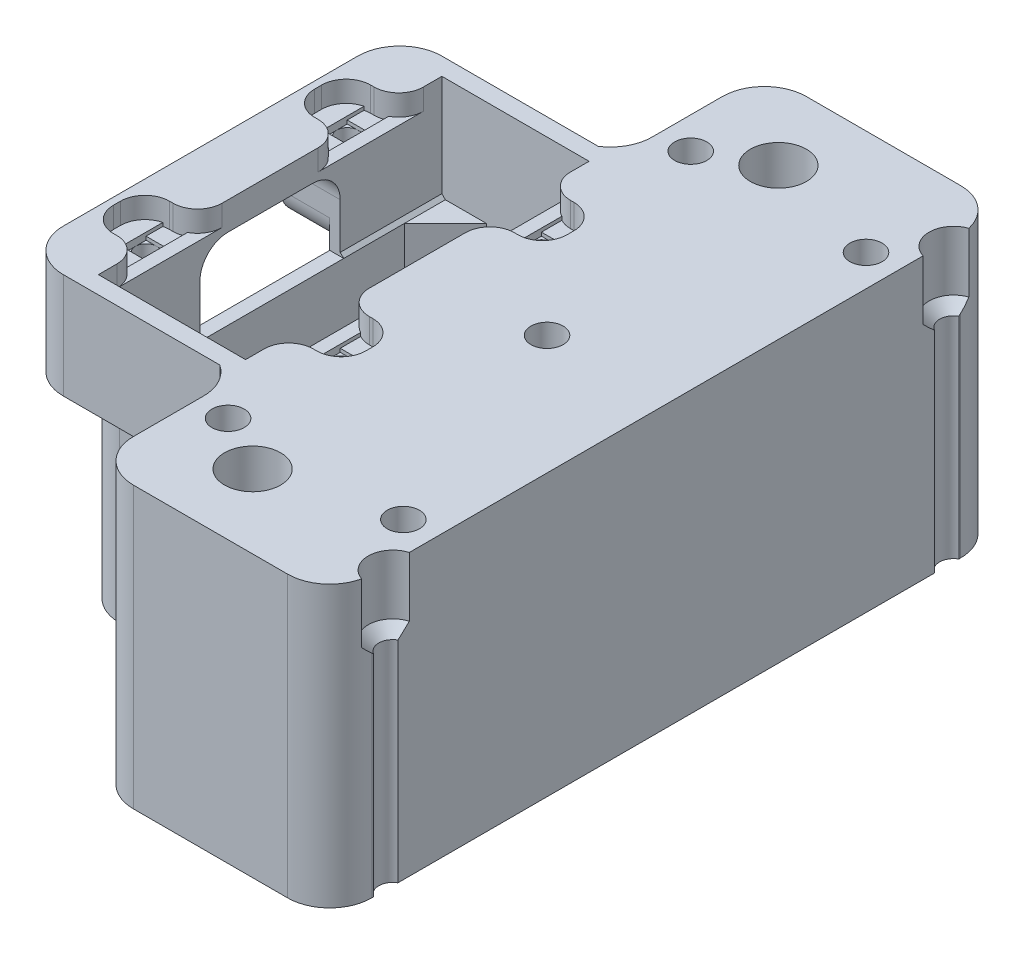
SolidWorks part; units mm, degrees
ref_plane "Płaszczyzna przednia" through (0, 0, 0) normal (0, 0, 1) x (1, 0, 0)
ref_plane "Płaszczyzna górna" through (0, 0, 0) normal (0, 1, 0) x (1, 0, 0)
ref_plane "Płaszczyzna prawa" through (0, 0, 0) normal (1, 0, 0) x (0, 0, -1)
sketch "Szkic1" plane through (0, 0, 0) normal (0, 1, 0) x (1, 0, 0)
  line L0 (0, 14.5) -> (0, -14.5) construction
  line L1 (10, 14.5) -> (10, -14.5)
  line L2 (-10, 14.5) -> (-10, -14.5)
  line L4 (-12, 26) -> (12, 26)
  line L5 (-12, 26) -> (-12, -26)
  line L6 (-12, -26) -> (12, -26)
  line L7 (12, 26) -> (12, -26)
  line L8 (-12, 26) -> (12, -26) construction
  line L9 (-12, -26) -> (12, 26) construction
  arc A0 (10, 14.5) -> (-10, 14.5) centre (0, 14.5) ccw
  arc A1 (-10, -14.5) -> (10, -14.5) centre (0, -14.5) ccw
  point P2 (0, 0)
  point P8 (0, 0)
  dimension "D2" = 10
  dimension "D1" = 29
  dimension "D3" = 24
  dimension "D4" = 52
extrude "Dodanie-wyciągnięcie1" add sketch "Szkic1" along normal blind 25
sketch "Szkic2" plane through (0, 25, 0) normal (0, 1, 0) x (1, 0, 0)
  line L1 (-10.5, 24.5) -> (10.5, 24.5)
  line L2 (-10.5, 24.5) -> (-10.5, -24.5)
  line L3 (-10.5, -24.5) -> (10.5, -24.5)
  line L4 (10.5, 24.5) -> (10.5, -24.5)
  line L5 (-10.5, 24.5) -> (10.5, -24.5) construction
  line L6 (-10.5, -24.5) -> (10.5, 24.5) construction
  line L7 (-13, 27) -> (13, 27)
  line L8 (-13, 27) -> (-13, -27)
  line L9 (-13, -27) -> (13, -27)
  line L10 (13, 27) -> (13, -27)
  line L11 (-13, 27) -> (13, -27) construction
  line L12 (-13, -27) -> (13, 27) construction
  point P0 (0, 0)
  point P7 (0, 0)
  dimension "D1" = 26
  dimension "D2" = 54
  dimension "D3" = 21
  dimension "D4" = 49
extrude "Dodanie-wyciągnięcie2" add sketch "Szkic2" along normal blind 12
sketch "Szkic3" plane through (0, 37, 0) normal (0, 1, 0) x (1, 0, 0)
  line L0 (13, -27) -> (13, 27) construction
  line L1 (-19, 27) -> (19, 27)
  line L2 (-19, 27) -> (-19, -27)
  line L3 (-19, -27) -> (19, -27)
  line L4 (19, 27) -> (19, -27)
  line L5 (-19, 27) -> (19, -27) construction
  line L6 (-19, -27) -> (19, 27) construction
  line L7 (-13, -27) -> (13, -27) construction
  line L9 (-10.5, 24.5) -> (10.5, 24.5)
  line L10 (-10.5, 24.5) -> (-10.5, -24.5)
  line L11 (-10.5, -24.5) -> (10.5, -24.5)
  line L12 (10.5, 24.5) -> (10.5, -24.5)
  line L13 (-10.5, 24.5) -> (10.5, -24.5) construction
  line L14 (-10.5, -24.5) -> (10.5, 24.5) construction
  point P0 (0, 0)
  point P10 (0, 0)
  dimension "D1" = 6
extrude "Dodanie-wyciągnięcie3" add sketch "Szkic3" against normal blind 12
sketch "Szkic4" plane through (0, 37, 0) normal (0, 1, 0) x (1, 0, 0)
  line L0 (10, 24.5) -> (-10, 24.5)
  line L1 (-19, 27) -> (19, 27)
  line L2 (-19, 27) -> (-19, -27)
  line L3 (-19, -27) -> (19, -27)
  line L4 (19, 27) -> (19, -27)
  line L5 (-19, 27) -> (19, -27) construction
  line L6 (-19, -27) -> (19, 27) construction
  line L7 (10.5, 24.5) -> (-10.5, 24.5) construction
  line L8 (-10, 24.5) -> (-10, 18.35)
  line L9 (-10, 18.35) -> (-18, 18.35)
  line L10 (-18, 18.35) -> (-18, 10.35)
  line L11 (-18, 10.35) -> (-10, 10.35)
  line L12 (-10, 10.35) -> (-10, -10.35)
  line L13 (-10, -10.35) -> (-18, -10.35)
  line L14 (-18, -10.35) -> (-18, -18.35)
  line L15 (-18, -18.35) -> (-10, -18.35)
  line L16 (10, -24.5) -> (-10, -24.5)
  line L17 (-10.5, -24.5) -> (10.5, -24.5) construction
  line L18 (-10, -24.5) -> (-10, -18.35)
  line L19 (0, -20.35) -> (0, 20.35) construction
  line L20 (10, -24.5) -> (10, -18.35)
  line L21 (18, -18.35) -> (10, -18.35)
  line L22 (18, -10.35) -> (18, -18.35)
  line L23 (10, -10.35) -> (18, -10.35)
  line L24 (10, 10.35) -> (10, -10.35)
  line L25 (18, 10.35) -> (10, 10.35)
  line L26 (18, 18.35) -> (18, 10.35)
  line L27 (10, 18.35) -> (18, 18.35)
  line L28 (10, 24.5) -> (10, 18.35)
  line L29 (19, 27) -> (19, -27)
  point P0 (0, 0)
  point P24 (-18, -14.35)
  point P25 (-18, 14.35)
  point P29 (0, -24.5)
  point P37 (0, 24.5)
  line M8 (-19, -27) -> (19, -27)
  line M9 (19, -27) -> (19, 27)
  line M10 (19, 27) -> (-19, 27)
  line M11 (-19, 27) -> (-19, -27)
  line M12 (-10.5, 24.5) -> (10.5, 24.5)
  line M13 (10.5, 24.5) -> (10.5, -24.5)
  line M14 (10.5, -24.5) -> (-10.5, -24.5)
  line M15 (-10.5, -24.5) -> (-10.5, 24.5)
  dimension "D1" = 8
  dimension "D2" = 8
  dimension "D3" = 28.7
  dimension "D4" = 8
  dimension "D5" = 1
extrude "Dodanie-wyciągnięcie4" add sketch "Szkic4" along normal blind 3 contours L27 L26 L25 L23 L22 L21 L15 L14 L13 L11 L10 L9 M11 M8 M9 M10 M13 M14 M15 M12 region at (0, 37, -26.3397)
fillet "Zaokrąglenie1" radius 3.5 16 edges at (-18, 38.5, -10.35) (-18, 38.5, -18.35) (-18, 38.5, 10.35) (-18, 38.5, 18.35) (18, 38.5, -10.35) (18, 38.5, -18.35) (18, 38.5, 10.35) (18, 38.5, 18.35) (10.5, 38.5, 10.35) (10.5, 38.5, 18.35) (10.5, 38.5, -18.35) (10.5, 38.5, -10.35) (-10.5, 38.5, -18.35) (-10.5, 38.5, -10.35) (-10.5, 38.5, 10.35) (-10.5, 38.5, 18.35)
sketch "Szkic5" plane through (0, 37, 0) normal (0, 1, 0) x (1, 0, 0)
  line L0 (18, -14.35) -> (13.85, -14.35) construction
  line L3 (18, -13.85) -> (18, -14.85) construction
  line L6 (18, 14.35) -> (13.85, 14.35) construction
  line L9 (18, 14.85) -> (18, 13.85) construction
  line L13 (0, -22) -> (0, 22) construction
  circle A0 centre (13.85, -14.35) radius 1.5
  circle A1 centre (13.85, 14.35) radius 1.5
  circle A2 centre (-13.85, -14.35) radius 1.5
  circle A3 centre (-13.85, 14.35) radius 1.5
  dimension "D1" = 3
  dimension "D2" = 3
  dimension "D3" = 4.15
  dimension "D4" = 4.15
extrude "Wytnij-wyciągnięcie1" cut sketch "Szkic5" against normal blind 8
sketch "Szkic7" plane through (-19, 0, 0) normal (-1, 0, 0) x (0, 0, 1)
  line L1 (-10, 36) -> (10, 36)
  line L2 (-10, 36) -> (-10, 25)
  line L3 (-10, 25) -> (10, 25)
  line L4 (10, 36) -> (10, 25)
  line L5 (-10, 36) -> (10, 25) construction
  line L6 (-10, 25) -> (10, 36) construction
  line L7 (0, 30.5) -> (0, 40) construction
  line L10 (-27, 40) -> (27, 40) construction
  line L12 (-27, 25) -> (27, 25) construction
  point P0 (0, 30.5)
  dimension "D1" = 20
  dimension "D2" = 11
extrude "Wytnij-wyciągnięcie2" cut sketch "Szkic7" against normal up to next
sketch "Szkic8" plane through (0, 0, 0) normal (0, 1, 0) x (1, 0, 0)
  line L1 (12, -48) -> (46, -48)
  line L2 (12, -48) -> (12, 48)
  line L3 (12, 48) -> (46, 48)
  line L4 (46, -48) -> (46, 48)
  line L5 (12, -48) -> (46, 48) construction
  line L6 (12, 48) -> (46, -48) construction
  line L8 (14, 46) -> (44, 46)
  line L9 (14, 46) -> (14, -46)
  line L10 (14, -46) -> (44, -46)
  line L11 (44, 46) -> (44, -46)
  line L12 (14, 46) -> (44, -46) construction
  line L13 (14, -46) -> (44, 46) construction
  line L14 (12, -26) -> (12, 26) construction
  line L15 (29, 0) -> (0, 0) construction
  point P0 (29, 0)
  point P12 (29, 0)
  dimension "D2" = 34
  dimension "D3" = 96
  dimension "D4" = 92
  dimension "D5" = 30
extrude "Dodanie-wyciągnięcie5" add sketch "Szkic8" along normal blind 18.5
sketch "Szkic9" plane through (0, 18.5, 0) normal (0, 1, 0) x (1, 0, 0)
  line L1 (12, -48) -> (46, -48)
  line L2 (12, -48) -> (12, 48)
  line L3 (12, 48) -> (46, 48)
  line L4 (46, -48) -> (46, 48)
  line L5 (12, -48) -> (46, 48) construction
  line L6 (12, 48) -> (46, -48) construction
  point P4 (29, 0)
extrude "Dodanie-wyciągnięcie6" add sketch "Szkic9" along normal blind 3
sketch "Szkic10" plane through (0, 21.5, 0) normal (0, 1, 0) x (1, 0, 0)
  line L0 (0, 0) -> (29, 0) construction
  line L1 (12, -26) -> (12, -48) construction
  line L4 (24.5, -37.5) -> (24.5, 37.5) construction
  circle A0 centre (24.5, 37.5) radius 1.9
  circle A1 centre (24.5, -37.5) radius 1.9
  point P13 (24.5, 0)
  dimension "D2" = 3.8
  dimension "D3" = 3.8
  dimension "D1" = 75
  dimension "D4" = 12.5
extrude "Wytnij-wyciągnięcie3" cut sketch "Szkic10" against normal through all
fillet "Zaokrąglenie2" radius 5 4 edges at (14, 9.25, -46) (44, 9.25, -46) (44, 9.25, 46) (14, 9.25, 46)
sketch "Szkic11" plane through (0, 21.5, 0) normal (0, 1, 0) x (1, 0, 0)
  line L1 (12, -48) -> (46, -48)
  line L2 (12, -48) -> (12, 48)
  line L3 (12, 48) -> (46, 48)
  line L4 (46, -48) -> (46, 48)
  line L5 (12, -48) -> (46, 48) construction
  line L6 (12, 48) -> (46, -48) construction
  circle A0 centre (24.5, 37.5) radius 4
  circle A1 centre (24.5, -37.5) radius 4
  point P10 (29, 0)
  dimension "D1" = 8
  dimension "D2" = 8
extrude "Dodanie-wyciągnięcie7" add sketch "Szkic11" along normal up to surface (3.5 mm away) up to face at (-5.1667, 25, 0)
sketch "Szkic12" plane through (0, 25, 0) normal (0, 1, 0) x (1, 0, 0)
  line L0 (10, -14.5) -> (10, 14.5)
  line L1 (10, -14.5) -> (10, 14.5)
  line L2 (-10, 14.5) -> (-10, -14.5)
  line L3 (-10, 14.5) -> (-10, -14.5)
  line L4 (-19, 10) -> (-19, 27)
  line L5 (-19, 10) -> (-19, 27)
  line L6 (-19, 27) -> (12, 27)
  line L7 (-19, 27) -> (12, 27)
  line L8 (12, 27) -> (12, 48)
  line L9 (12, 27) -> (12, 48)
  line L10 (12, 48) -> (46, 48)
  line L11 (12, 48) -> (46, 48)
  line L12 (46, 48) -> (46, -48)
  line L13 (46, 48) -> (46, -48)
  line L14 (46, -48) -> (12, -48)
  line L15 (46, -48) -> (12, -48)
  line L16 (12, -48) -> (12, -27)
  line L17 (12, -48) -> (12, -27)
  line L18 (12, -27) -> (-19, -27)
  line L19 (12, -27) -> (-19, -27)
  line L20 (-19, -27) -> (-19, -10)
  line L21 (-19, -27) -> (-19, -10)
  line L22 (-19, -10) -> (-19, 10)
  line L23 (-19, -10) -> (-19, 10)
  circle A0 centre (24.5, 37.5) radius 1.9
  circle A1 centre (24.5, 37.5) radius 1.9
  circle A2 centre (24.5, -37.5) radius 1.9
  circle A3 centre (24.5, -37.5) radius 1.9
  arc A4 (10, 14.5) -> (-10, 14.5) centre (0, 14.5) ccw
  arc A5 (10, 14.5) -> (-10, 14.5) centre (0, 14.5) ccw
  arc A6 (-10, -14.5) -> (10, -14.5) centre (0, -14.5) ccw
  arc A7 (-10, -14.5) -> (10, -14.5) centre (0, -14.5) ccw
  circle M11 centre (24.5, 37.5) radius 4
  circle M12 centre (24.5, -37.5) radius 4
  line M13 (12, 27) -> (19, 27)
  line M14 (19, 27) -> (19, -27)
  line M15 (19, -27) -> (12, -27)
  line M16 (12, -27) -> (12, -48)
  line M17 (12, -48) -> (46, -48)
  line M18 (46, -48) -> (46, 48)
  line M19 (46, 48) -> (12, 48)
  line M20 (12, 48) -> (12, 27)
extrude "Dodanie-wyciągnięcie8" add sketch "Szkic12" along normal up to surface (15 mm away) contours M20 M13 M14 M15 M16 M17 M18 M19 M12 M11 region at (30.9944, 25, 0) up to face at (0, 40, 0)
sketch "Szkic13" plane through (0, 40, 0) normal (0, 1, 0) x (1, 0, 0)
  line L0 (29, 48) -> (29, -48) construction
  line L1 (46, 48) -> (12, 48) construction
  line L2 (12, -48) -> (46, -48) construction
  line L3 (29, 0) -> (41.5, 0) construction
  line L4 (41.5, 33) -> (41.5, -33) construction
  circle A0 centre (41.5, 33) radius 2.3
  circle A1 centre (41.5, -33) radius 2.3
  circle A2 centre (16.5, -33) radius 2.3
  circle A3 centre (16.5, 33) radius 2.3
  circle A4 centre (29, 0) radius 2.3
  point P12 (41.5, 0)
  dimension "D3" = 4.6
  dimension "D4" = 4.6
  dimension "D5" = 4.6
  dimension "D1" = 12.5
  dimension "D2" = 66
extrude "Wytnij-wyciągnięcie4" cut sketch "Szkic13" against normal blind 6
sketch "Szkic14" plane through (0, 25, 0) normal (0, 1, 0) x (1, 0, 0)
  line L0 (10, 0) -> (10, 18.6421)
  line L1 (10, -14.5) -> (10, 14.5) construction
  line L2 (-10.5, 24.5) -> (10.5, 24.5) construction
  line L3 (-4.1421, 24.5) -> (4.1421, 24.5)
  line L4 (10, 18.6421) -> (4.1421, 24.5)
  line L5 (4.1421, 24.5) -> (10, 24.5) construction
  line L6 (10, 18.6421) -> (10, 24.5) construction
  line L7 (10, 0) -> (10, -18.6421)
  line L8 (10.5, -24.5) -> (-10.5, -24.5) construction
  line L9 (4.1421, -24.5) -> (-4.1421, -24.5)
  line L10 (4.1421, -24.5) -> (10, -18.6421)
  line L11 (10, -18.6421) -> (10, -24.5) construction
  line L12 (10, -24.5) -> (4.1421, -24.5) construction
  line L13 (0, -22) -> (0, 22) construction
  line L14 (-10, 18.6421) -> (-4.1421, 24.5)
  line L15 (-10, 0) -> (-10, 18.6421)
  line L16 (-10, 0) -> (-10, -18.6421)
  line L17 (-4.1421, -24.5) -> (-10, -18.6421)
  arc A0 (10, 14.5) -> (0, 24.5) centre (0, 14.5) ccw construction
  arc A1 (0, -24.5) -> (10, -14.5) centre (0, -14.5) ccw construction
  point P25 (0, 24.5)
  point P29 (0, -24.5)
  dimension "D1" = 45
  dimension "D2" = 45
extrude "Wytnij-wyciągnięcie5" cut sketch "Szkic14" against normal through all
chamfer "Sfazowanie1" distance 0.5 angle 45 3 edges at (10.5, 25, 0) (-10.5, 25, 17.25) (-10.5, 25, -17.25)
sketch "Szkic15" plane through (0, 37, 0) normal (0, 1, 0) x (1, 0, 0)
  line L1 (12.35, -15.85) -> (15.35, -15.85)
  line L2 (12.35, -15.85) -> (12.35, -12.85)
  line L3 (12.35, -12.85) -> (15.35, -12.85)
  line L4 (15.35, -15.85) -> (15.35, -12.85)
  line L5 (12.35, -15.85) -> (15.35, -12.85) construction
  line L6 (12.35, -12.85) -> (15.35, -15.85) construction
  line L7 (12.35, 12.85) -> (15.35, 12.85)
  line L8 (12.35, 12.85) -> (12.35, 15.85)
  line L9 (12.35, 15.85) -> (15.35, 15.85)
  line L10 (15.35, 12.85) -> (15.35, 15.85)
  line L11 (12.35, 12.85) -> (15.35, 15.85) construction
  line L12 (12.35, 15.85) -> (15.35, 12.85) construction
  line L13 (-15.35, 12.85) -> (-12.35, 12.85)
  line L14 (-15.35, 12.85) -> (-15.35, 15.85)
  line L15 (-15.35, 15.85) -> (-12.35, 15.85)
  line L16 (-12.35, 12.85) -> (-12.35, 15.85)
  line L17 (-15.35, 12.85) -> (-12.35, 15.85) construction
  line L18 (-15.35, 15.85) -> (-12.35, 12.85) construction
  line L19 (-15.35, -15.85) -> (-12.35, -15.85)
  line L20 (-15.35, -15.85) -> (-15.35, -12.85)
  line L21 (-15.35, -12.85) -> (-12.35, -12.85)
  line L22 (-12.35, -15.85) -> (-12.35, -12.85)
  line L23 (-15.35, -15.85) -> (-12.35, -12.85) construction
  line L24 (-15.35, -12.85) -> (-12.35, -15.85) construction
  point P0 (13.85, -14.35)
  point P6 (13.85, 14.35)
  point P12 (-13.85, 14.35)
  point P18 (-13.85, -14.35)
extrude "Wytnij-wyciągnięcie6" cut sketch "Szkic15" against normal blind 1
sketch "Szkic16" plane through (0, 37, 0) normal (0, 1, 0) x (1, 0, 0)
  line L0 (-14.5, -18.35) -> (-14, -18.35) construction
  line L1 (-15.35, -19.123) -> (-12.35, -19.123) construction
  line L2 (-15.35, -18.2452) -> (-15.35, -10.4548)
  line L3 (-15.35, -9.577) -> (-12.35, -9.577) construction
  line L4 (-12.35, -18.7633) -> (-12.35, -9.9367)
  line L5 (-15.0913, -18.2997) -> (-12.35, -9.577) construction
  line L6 (-15.0913, -10.4003) -> (-12.4845, -18.6951) construction
  line L7 (-14, -10.35) -> (-14.5, -10.35) construction
  line L8 (-14.5, -18.35) -> (-14, -18.35)
  line L9 (-14, -10.35) -> (-14.5, -10.35)
  line L10 (-15.35, -9.577) -> (-15.0913, -10.4003) construction
  line L11 (-15.35, -10.4548) -> (-15.35, -9.577) construction
  line L12 (-12.35, -9.9367) -> (-12.35, -9.577) construction
  line L13 (-15.35, -19.123) -> (-15.35, -18.2452) construction
  line L14 (-15.35, -19.123) -> (-15.0913, -18.2997) construction
  line L15 (-12.35, -19.123) -> (-12.35, -18.7633) construction
  line L16 (-12.4845, -18.6951) -> (-12.35, -19.123) construction
  line L17 (-15.35, -12.85) -> (-15.35, -15.85) construction
  line L19 (-20.9, 0) -> (20.9, 0) construction
  line L20 (-14.5, 18.35) -> (-14, 18.35)
  line L21 (-15.35, 18.2452) -> (-15.35, 10.4548)
  line L22 (-14, 10.35) -> (-14.5, 10.35)
  line L23 (-12.35, 18.7633) -> (-12.35, 9.9367)
  arc A0 (-10.5, -21.85) -> (-14, -18.35) centre (-14, -21.85) ccw construction
  arc A1 (-18, -14.85) -> (-14.5, -18.35) centre (-14.5, -14.85) ccw construction
  arc A2 (-14.5, -10.35) -> (-18, -13.85) centre (-14.5, -13.85) ccw construction
  arc A3 (-14, -10.35) -> (-10.5, -6.85) centre (-14, -6.85) ccw construction
  arc A4 (-12.35, -18.7633) -> (-14, -18.35) centre (-14, -21.85) ccw
  arc A5 (-15.35, -18.2452) -> (-14.5, -18.35) centre (-14.5, -14.85) ccw
  arc A6 (-14.5, -10.35) -> (-15.35, -10.4548) centre (-14.5, -13.85) ccw
  arc A7 (-14, -10.35) -> (-12.35, -9.9367) centre (-14, -6.85) ccw
  arc A8 (-12.35, -9.9367) -> (-10.5, -6.85) centre (-14, -6.85) ccw construction
  arc A9 (-15.35, -10.4548) -> (-18, -13.85) centre (-14.5, -13.85) ccw construction
  arc A10 (-18, -14.85) -> (-15.35, -18.2452) centre (-14.5, -14.85) ccw construction
  arc A11 (-10.5, -21.85) -> (-12.35, -18.7633) centre (-14, -21.85) ccw construction
  arc A12 (-12.35, 18.7633) -> (-14, 18.35) centre (-14, 21.85) cw
  arc A13 (-15.35, 18.2452) -> (-14.5, 18.35) centre (-14.5, 14.85) cw
  arc A14 (-14.5, 10.35) -> (-15.35, 10.4548) centre (-14.5, 13.85) cw
  arc A15 (-14, 10.35) -> (-12.35, 9.9367) centre (-14, 6.85) cw
  point P0 (-13.85, -14.35)
extrude "Wytnij-wyciągnięcie7" cut sketch "Szkic16" against normal blind 0.5
mirror "Lustro1" about plane through (0, 0, 0) normal (1, 0, 0) of "Wytnij-wyciągnięcie7"
chamfer "Sfazowanie2" distance 2.1 angle 45 2 edges at (24.5, 21.5, -33.5) (24.5, 21.5, 41.5)
fillet "Zaokrąglenie3" radius 6 10 edges at (12, 12.5, 26) (12, 12.5, -26) (-19, 32.5, 27) (-19, 32.5, -27) (-12, 12.5, -26) (-12, 12.5, 26) (12, 20, -48) (46, 20, -48) (46, 20, 48) (12, 20, 48)
fillet "Zaokrąglenie4" radius 4 4 edges at (-14.75, 36, 10) (-15.5, 25, 10) (-14.75, 36, -10) (-15.5, 25, -10)
sketch "Szkic18" plane through (0, 40, 0) normal (0, 1, 0) x (1, 0, 0)
  line L0 (46, 0) -> (47, 0) construction
  line L1 (46, -42) -> (46, 42) construction
  line L2 (47, 0) -> (47, 40) construction
  circle A0 centre (47, 40) radius 3.5
  circle A1 centre (47, -40) radius 3.5
  dimension "D1" = 7
  dimension "D2" = 1
  dimension "D3" = 40
extrude "Wytnij-wyciągnięcie8" cut sketch "Szkic18" against normal blind 10
chamfer "Sfazowanie3" distance 1.5 angle 45 2 edges at (43.5008, 30, -39.9242) (43.5008, 30, 39.9242)
sketch "Szkic19" plane through (0, 30, 0) normal (0, 1, 0) x (1, 0, 0)
  circle A0 centre (47, -40) radius 2
  circle A1 centre (47, 40) radius 2
  arc A2 (46, 41.7321) -> (46, 38.2679) centre (47, 40) ccw construction
extrude "Wytnij-wyciągnięcie9" cut sketch "Szkic19" against normal through all
